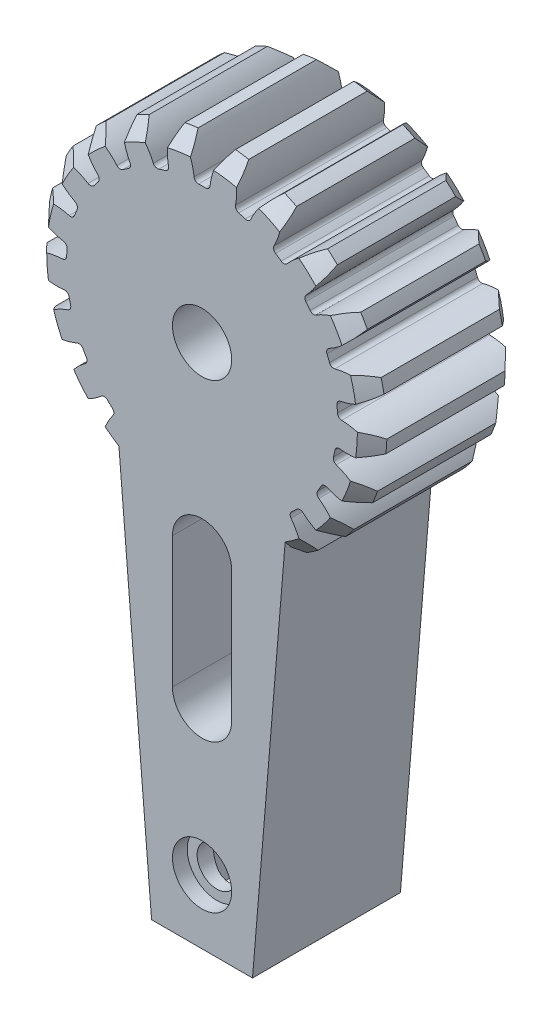
SolidWorks part; units mm, degrees
material "Acier non allié"
ref_plane "Plan de face" through (0, 0, 0) normal (0, 0, 1) x (1, 0, 0)
ref_plane "Plan de dessus" through (0, 0, 0) normal (0, 1, 0) x (1, 0, 0)
ref_plane "Plan de droite" through (0, 0, 0) normal (1, 0, 0) x (0, 0, -1)
sketch "Esquisse1" plane through (0, 0, 0) normal (0, 0, 1) x (1, 0, 0)
  line L0 (7, 8.75) -> (-7, 8.75)
  line L1 (-7, 8.75) -> (-7, 2.6926)
  line L2 (-7.4743, -0.6198) -> (-4.9832, -30.6632)
  line L3 (0, 8.75) -> (0, -35.25) construction
  line L4 (7.4743, -0.6198) -> (4.9832, -30.6632)
  line L5 (7, 8.75) -> (7, 2.6926)
  line L6 (9.4675, -0.785) -> (6.9764, -30.8284)
  line L7 (-9.4675, -0.785) -> (-6.9764, -30.8284)
  line L8 (-9, 10.75) -> (-9, 3.0414)
  line L9 (9, 10.75) -> (-9, 10.75)
  line L10 (9, 10.75) -> (9, 3.0414)
  line L11 (-6.9764, -30.8284) -> (-5.1172, -53.25)
  line L12 (-5.1172, -53.25) -> (5.1172, -53.25)
  line L13 (5.1172, -53.25) -> (6.9764, -30.8284)
  line L14 (7.9726, -0.6611) -> (5.4815, -30.7045)
  line L15 (-7.9726, -0.6611) -> (-5.4815, -30.7045)
  line L16 (-7.5, 9.25) -> (-7.5, 2.7839)
  line L17 (7.5, 9.25) -> (-7.5, 9.25)
  line L18 (7.5, 9.25) -> (7.5, 2.7839)
  arc A0 (-7, 2.6926) -> (-7.4743, -0.6198) centre (0, 0) ccw
  arc A1 (-4.9832, -30.6632) -> (0, -35.25) centre (-0.0003, -30.25) ccw
  circle A2 centre (0, 0) radius 7.5 construction
  arc A3 (4.9832, -30.6632) -> (0, -35.25) centre (0.0003, -30.25) cw
  arc A4 (7, 2.6926) -> (7.4743, -0.6198) centre (0, 0) cw
  arc A7 (-9, 3.0414) -> (-9.4675, -0.785) centre (0, 0) ccw
  arc A8 (9, 3.0414) -> (9.4675, -0.785) centre (0, 0) cw
  circle A11 centre (0, -25.11) radius 1.5
  circle A12 centre (0, -19.97) radius 1.5
  circle A13 centre (-0.0003, -30.25) radius 1.5
  circle A14 centre (0, 0) radius 1.5
  arc A15 (6.9764, -30.8284) -> (0, -37.25) centre (0.0003, -30.25) cw construction
  arc A16 (-6.9764, -30.8284) -> (0, -37.25) centre (-0.0003, -30.25) ccw construction
  arc A17 (5.4815, -30.7045) -> (0, -35.75) centre (0.0003, -30.25) cw
  arc A18 (-5.4815, -30.7045) -> (0, -35.75) centre (-0.0003, -30.25) ccw
  arc A19 (-7.5, 2.7839) -> (-7.9726, -0.6611) centre (0, 0) ccw
  arc A20 (7.5, 2.7839) -> (7.9726, -0.6611) centre (0, 0) cw
  dimension "D3" = 5
  dimension "D4" = 15
  dimension "D5" = 44
  dimension "D9" = 5.14
  dimension "D10" = 3
  dimension "D12" = 3
  dimension "D1" = 8.75
  dimension "D2" = 7
  dimension "D6" = 4.74
  dimension "D8" = 19.97
  dimension "D11" = 5.14
  dimension "D13" = 18
  dimension "D7" = 2
  dimension "D14" = 0.5
sketch "Esquisse2" plane through (0, 0, 0) normal (0, 0, 1) x (1, 0, 0)
  circle A0 centre (0, 0) radius 17.25
  circle A1 centre (0, 0) radius 15.75 construction
  dimension "D1" = 34.5
  dimension "D2" = 31.5
extrude "Boss.-Extru.1" add sketch "Esquisse2" along normal blind 15
sketch "Esquisse3" plane through (0, 0, 0) normal (0, 0, 1) x (1, 0, 0)
  line L0 (0, 17.25) -> (0, 0) construction
  line L1 (0, 0) -> (5.0845, 16.4836) construction
  line L2 (0, 0) -> (3.9615, 26.2831) construction
  line L3 (-0.7708, 13.7284) -> (0, 0) construction
  line L4 (-1.177, 15.706) -> (1.177, 15.706) construction
  line L5 (1.177, 15.706) -> (3.5047, 15.3551) construction
  line L6 (-1.7081, 17.1652) -> (0, 12.4722) construction
  arc A0 (1.9004, 17.145) -> (-1.9004, 17.145) centre (0, 0) ccw
  circle A1 centre (0, 0) radius 14.25
  arc A3 (-1.9004, 17.145) -> (-0.7708, 13.7284) centre (-7.6755, 13.3407) cw
  arc A4 (1.9004, 17.145) -> (0.7708, 13.7284) centre (7.6755, 13.3407) ccw
  circle A5 centre (0, 0) radius 17.25 construction
  circle A6 centre (0, 0) radius 15.75 construction
  arc A7 (0.7708, 13.7284) -> (-0.7708, 13.7284) centre (0, 0) ccw
  dimension "D1" = 17.143
  dimension "D5" = 20
  dimension "D3" = 0.5
extrude "Enlèv. mat.-Extru.2" cut sketch "Esquisse3" against normal blind 15 and the other way through all contours A3 A7 A4 A0
fillet "Congé1" radius 0.45 2 edges at (0.7708, 13.7284, 7.5) (-0.7708, 13.7284, 7.5)
chamfer "Chanfrein1" distance 1.5 2 edges at (0, -17.25, 15) (0, -17.25, 0)
pattern_circular "Répétition circulaire1" count 21 over 360 about axis through (0, 0, 15) along (0, 0, -1) of "Congé1", "Enlèv. mat.-Extru.2"
extrude "Boss.-Extru.2" add sketch "Esquisse1" along normal blind 15 contours L6 L13 L12 L11 L7 A7 L8 L9 L10 A8
extrude "Enlèv. mat.-Extru.3" cut sketch "Esquisse1<3>" along normal blind 6.4028 contours A17 A18 L15 A19 L16 L17 L18 A20 L14
sketch "Esquisse1<3>" plane through (0, 0, 0) normal (0, 0, 1) x (1, 0, 0) same geometry as "Esquisse1"
extrude "Enlèv. mat.-Extru.4" cut sketch "Esquisse1<4>" along normal through all contours A14 | A13 | A11 | A12
sketch "Esquisse1<4>" plane through (0, 0, 0) normal (0, 0, 1) x (1, 0, 0) same geometry as "Esquisse1"
sketch "Esquisse5" plane through (0, 0, 0) normal (0, 0, 1) x (1, 0, 0)
  line L0 (0, -31.75) -> (0, -18.47) construction
  line L1 (-3, -31.75) -> (-3, -18.47)
  line L2 (3, -31.75) -> (3, -18.47)
  circle A0 centre (0, 0) radius 3
  arc A4 (-3, -31.75) -> (3, -31.75) centre (0, -31.75) ccw
  arc A5 (3, -18.47) -> (-3, -18.47) centre (0, -18.47) ccw
  circle A6 centre (0, -19.97) radius 1.5 construction
  point P6 (0, -25.11)
  dimension "D1" = 6
  dimension "D2" = 3
extrude "Enlèv. mat.-Extru.8" cut sketch "Esquisse5" against normal blind 6.5028 from surface starting at face at (1.5, 0, 15)
sketch "Esquisse6" plane through (0, 0, 0) normal (0, 0, 1) x (1, 0, 0)
  line L0 (-7.5, 2.7839) -> (-7.5, 9.25)
  line L1 (-7.5, 9.25) -> (7.5, 9.25)
  line L2 (7.5, 9.25) -> (7.5, 2.7839)
  line L3 (7.5, 9.25) -> (7.5, 2.7839) construction
  line L4 (7.5, 9.25) -> (-7.5, 9.25) construction
  line L5 (-7.5, 9.25) -> (-7.5, 2.7839) construction
  arc A0 (-7.5, 2.7839) -> (7.5, 2.7839) centre (0, 0) ccw
  arc A1 (7.9726, -0.6611) -> (7.5, 2.7839) centre (0, 0) ccw construction
extrude "Enlèv. mat.-Extru.9" cut sketch "Esquisse6" along normal blind 1.48 from surface starting at face at (-1.5, 0, 6.4028)
ref_plane "Plan1" through (0, -53.25, 0) normal (0, -1, 0) x (-1, 0, 0)
sketch "Esquisse7" plane through (0, -53.25, 0) normal (0, -1, 0) x (-1, 0, 0)
  line L0 (0, 0) -> (0, -15) construction
  line L1 (5.1172, -15) -> (-5.1172, -15) construction
  line L3 (5.1172, -15) -> (-5.1172, -15)
  line L4 (5.1172, -15) -> (5.1172, 0)
  line L5 (5.1172, 0) -> (-5.1172, 0)
  line L6 (-5.1172, -15) -> (-5.1172, 0)
  line L7 (5.1172, -15) -> (-5.1172, 0) construction
  line L8 (5.1172, 0) -> (-5.1172, -15) construction
  circle A0 centre (0, -7.5) radius 4.8
  dimension "D1" = 9.6
ref_axis "Axe2" through (-8.4294, -13.3044, 15) along (0.0826, -0.9966, 0)
extrude "Enlèv. mat.-Extru.10" cut sketch "Esquisse7" against normal blind 13 from surface contours A0 starting at face at (0, -53.25, 7.5)
sketch "Esquisse11" plane through (0, 0, 0) normal (0, 0, 1) x (1, 0, 0)
  line L0 (0, 0) -> (0, -53.25) construction
  line L1 (-0.5661, -53.25) -> (0.5661, -53.25) construction
  circle A0 centre (0, -46.75) radius 2
  circle A1 centre (0, -46.75) radius 3
  dimension "D1" = 4
  dimension "D3" = 6
  dimension "D2" = 6.5
extrude "Enlèv. mat.-Extru.11" cut sketch "Esquisse11" along normal through all both and the other way through all contours A0
extrude "Enlèv. mat.-Extru.12" cut sketch "Esquisse11<4>" against normal blind 1.5 from surface starting at face at (2, -46.75, 15)
sketch "Esquisse11<4>" plane through (0, 0, 0) normal (0, 0, 1) x (1, 0, 0) same geometry as "Esquisse11"
extrude "Enlèv. mat.-Extru.13" cut sketch "Esquisse11<5>" along normal blind 1.5
sketch "Esquisse11<5>" plane through (0, 0, 0) normal (0, 0, 1) x (1, 0, 0) same geometry as "Esquisse11"
equation "\"Module\"= 1.5"
equation "\"Number of teeth\"= 21"
equation "\"Pressure Angle\"= 20"
equation "\"D1@Esquisse2\"=(\"Number of teeth\"+2)*\"Module\""
equation "\"D2@Esquisse2\"=\"Number of teeth\"*\"Module\""
equation "\"D1@Esquisse3\"=360/\"Number of teeth\""
equation "\"D2@Esquisse3\"=\"Module\"*2"
equation "\"D5@Esquisse3\"=\"Pressure Angle\""
equation "\"D1@Congé1\"=0.3*\"Module\""
equation "\"D1@Répétition circulaire1\"=\"Number of teeth\""
equation "\"D1@Chanfrein1\"=\"Module\""
